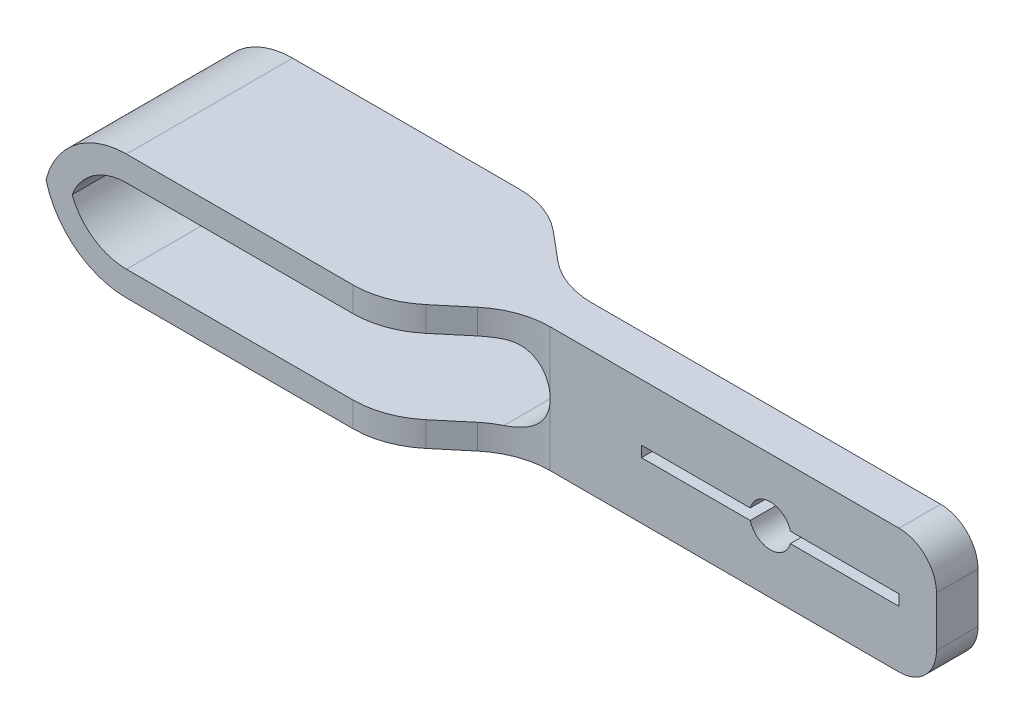
SolidWorks part; units mm, degrees
ref_plane "Plano frontal" through (0, 0, 0) normal (0, 0, 1) x (1, 0, 0)
ref_plane "Plano superior" through (0, 0, 0) normal (0, 1, 0) x (1, 0, 0)
ref_plane "Plano direito" through (0, 0, 0) normal (1, 0, 0) x (0, 0, -1)
sketch "Esboço1" plane through (0, 0, 0) normal (0, 0, 1) x (1, 0, 0)
  line L13 (-17.5, -6) -> (22.5, -6)
  line L14 (-17.5, -6) -> (-17.5, 9)
  line L15 (-17.5, 9) -> (22.5, 9)
  line L16 (22.5, -6) -> (22.5, 9)
  dimension "D3" = 15
  dimension "D4" = 40
extrude "Ressalto-extrusão1" add sketch "Esboço1" against normal blind 3 contours L13 L16 L15 L14 region at (2.5, 1.5, 0)
sketch "Esboço2" plane through (0, 0, 0) normal (0, 0, 1) x (1, 0, 0)
  line L0 (2.5, 1.5) -> (2.5, 9) construction
  line L1 (-17.5, 9) -> (22.5, 9) construction
  line L2 (0.086, 2.15) -> (-13, 2.15)
  line L3 (18, 2.15) -> (4.914, 2.15)
  line L4 (18, 2.15) -> (18, 0.85)
  line L5 (18, 0.85) -> (4.914, 0.85)
  line L6 (-13, 2.15) -> (-13, 0.85)
  line L7 (18, 2.15) -> (-13, 0.85) construction
  line L8 (18, 0.85) -> (-13, 2.15) construction
  line L9 (0.086, 0.85) -> (-13, 0.85)
  line L10 (22.5, -6) -> (22.5, 9) construction
  arc A1 (4.914, 2.15) -> (0.086, 2.15) centre (2.5, 1.5) ccw
  arc A18 (0.086, 0.85) -> (4.914, 0.85) centre (2.5, 1.5) ccw
  point P6 (22.5, 1.5)
  dimension "D1" = 5
  dimension "D2" = 31
  dimension "D3" = 1.3
sketch "Esboço3" plane through (0, 0, 0) normal (0, 0, 1) x (1, 0, 0)
  line L1 (-17.5, -6) -> (22.5, -6)
  line L2 (-17.5, -6) -> (-17.5, 9)
  line L3 (-17.5, 9) -> (22.5, 9)
  line L4 (22.5, -6) -> (22.5, 9)
extrude "Ressalto-extrusão2" add sketch "Esboço3" along normal blind 2
extrude "Corte-extrusão1" cut sketch "Esboço2" along normal up to surface and the other way up to surface up to face at (2.5, 1.5, 2) other way up to face at (2.5, 1.5, -3)
sketch "Esboço4" plane through (0, 9, 0) normal (0, 1, 0) x (1, 0, 0)
  line L0 (22.5, -2) -> (-17.5, -2) construction
  line L1 (6.2, -34.5) -> (-6.2, -34.5)
  line L2 (6.2, -34.5) -> (6.2, -11.5)
  line L3 (6.2, -11.5) -> (-6.2, -11.5)
  line L4 (-6.2, -34.5) -> (-6.2, -11.5)
  line L5 (-17.5, 3) -> (22.5, 3) construction
  line L6 (17.5, -2) -> (-12.5, -2)
  line L7 (17.5, -2) -> (17.5, -42)
  line L8 (17.5, -42) -> (-12.5, -42)
  line L9 (-12.5, -2) -> (-12.5, -42)
  line L10 (-12.5, -2) -> (17.5, -2)
  line L11 (-12.5, -2) -> (-12.5, 3)
  line L12 (-12.5, 3) -> (17.5, 3)
  line L13 (17.5, -2) -> (17.5, 3)
  circle A0 centre (0, -9.75) radius 1.25
  circle A1 centre (0, -36.25) radius 1.25
  point P6 (0, -34.5)
  point P13 (2.5, -2)
  point P14 (2.5, -42)
  line M5 (-17.5, -2) -> (22.5, -2)
  line M7 (22.5, 3) -> (-17.5, 3)
  dimension "D6" = 7.75
  dimension "D7" = 2.5
  dimension "D8" = 26.5
  dimension "D1" = 9.5
  dimension "D2" = 23
  dimension "D3" = 12.4
  dimension "D4" = 30
  dimension "D5" = 40
extrude "Ressalto-extrusão3" [suppressed] add sketch "Esboço4" against normal blind 3 contours L13 L11 M5 M7 | L9 L8 L7 L1 L4 L3 L2 M5
fillet "Filete2" [suppressed] radius 5
fillet "Filete3" [suppressed] radius 10
sketch "Esboço5" plane through (-17.5, 0, 0) normal (-1, 0, 0) x (0, 0, 1)
  line L0 (-3, 9) -> (2, 9) construction
  line L1 (-10.5, -6) -> (9.5, -6)
  line L2 (-10.5, -6) -> (-10.5, 9)
  line L3 (-10.5, 9) -> (9.5, 9)
  line L4 (9.5, -6) -> (9.5, 9)
  line L5 (-3, -6) -> (2, -6) construction
  point P13 (-0.5, -6)
  point P14 (-0.5, -6)
  dimension "D1" = 20
extrude "Ressalto-extrusão4" add sketch "Esboço5" along normal blind 60
chamfer "Chanfro1" distance 16 angle 50 2 edges at (-17.5, 1.5, 9.5) (-17.5, 1.5, -10.5) first distance on face at (-17.5, 1.5, 5.75) first distance on face at (-17.5, 1.5, -6.75)
fillet "Filete4" radius 10 6 edges at (-36.5681, 1.5, 9.5) (-27.6299, 1.5, 2) (-77.5, 9, -0.5) (-77.5, -6, -0.5) (-36.5681, 1.5, -10.5) (-27.6299, 1.5, -3)
sketch "Esboço6" plane through (0, 0, 9.5) normal (0, 0, 1) x (1, 0, 0)
  line L0 (-43.2078, 6) -> (-67.5, 6)
  line L1 (-67.5, -3) -> (-43.2078, -3)
  line L2 (-43.2078, -3) -> (-43.2078, 6) construction
  line L3 (-40.2078, 9) -> (-67.5, 9)
  line L4 (-67.5, -6) -> (-40.2078, -6)
  line L5 (-40.2078, -6) -> (-40.2078, 9)
  line L6 (-40.2078, 9) -> (-67.5, 9) construction
  line L7 (-67.5, -6) -> (-40.2078, -6) construction
  line L8 (-40.2078, -6) -> (-40.2078, 9) construction
  line L9 (-43.2078, 6) -> (-23.9902, 6)
  line L10 (-23.9902, 9) -> (-23.9902, -6) construction
  line L11 (-43.2078, -3) -> (-23.9902, -3)
  line L12 (-23.9902, -3) -> (-23.9902, 6)
  arc A0 (-67.5, 6) -> (-74.0383, 1.5) centre (-67.5, -1) ccw
  arc A1 (-74.0383, 1.5) -> (-67.5, -3) centre (-67.5, 4) ccw
  arc A2 (-67.5, 9) -> (-77.1825, 1.5) centre (-67.5, -1) ccw
  arc A3 (-77.1825, 1.5) -> (-67.5, -6) centre (-67.5, 4) ccw
  arc A4 (-67.5, 9) -> (-77.1825, 1.5) centre (-67.5, -1) ccw construction
  arc A5 (-77.1825, 1.5) -> (-67.5, -6) centre (-67.5, 4) ccw construction
  dimension "D1" = 0
  dimension "D2" = 3
extrude "Corte-extrusão2" cut sketch "Esboço6" against normal through all
fillet "Filete5" radius 4.5 4 edges at (-23.9902, -3, -0.5) (-23.9902, 6, -0.5) (22.5, -6, -0.5) (22.5, 9, -0.5)
